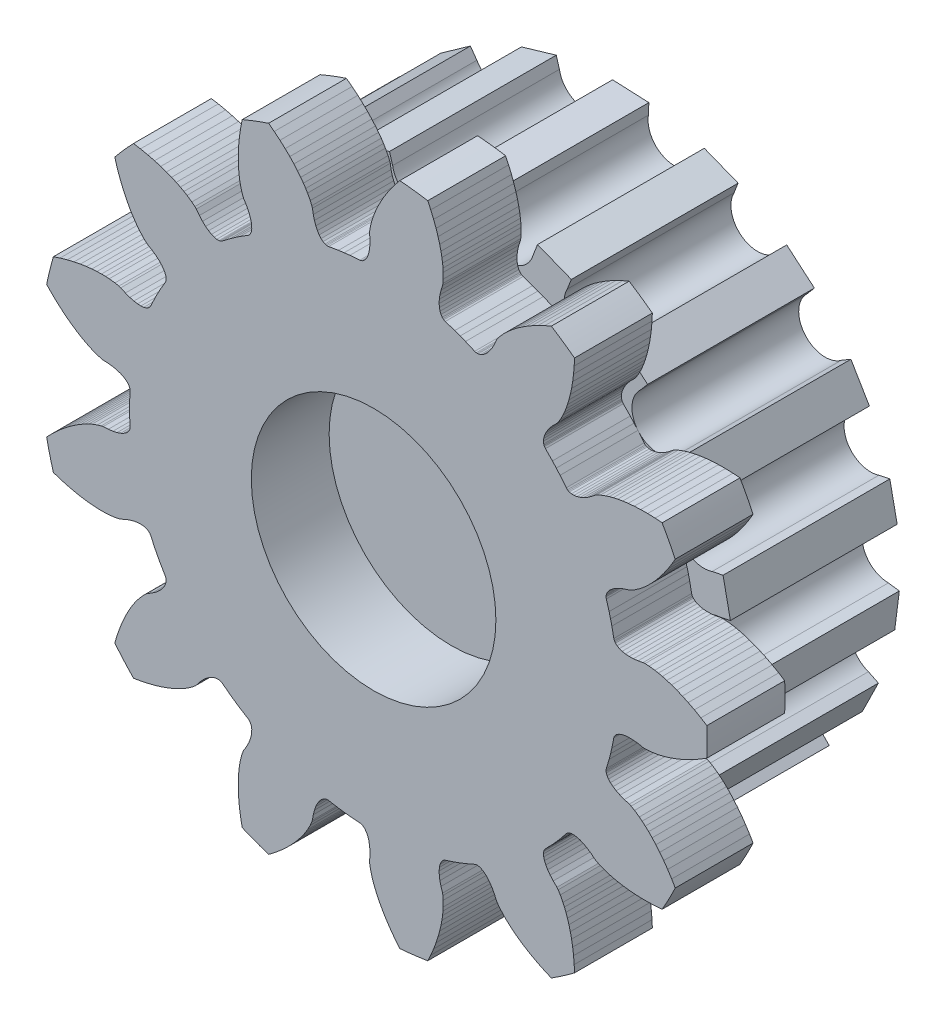
SolidWorks part; units mm, degrees
ref_plane "Front Plane" through (0, 0, 0) normal (0, 0, 1) x (1, 0, 0)
ref_plane "Top Plane" through (0, 0, 0) normal (0, 1, 0) x (1, 0, 0)
ref_plane "Right Plane" through (0, 0, 0) normal (1, 0, 0) x (0, 0, -1)
sketch "Model" plane through (0, 0, 0) normal (0, 0, 1) x (1, 0, 0)
  line L0 (54.9037, -18.3182) -> (55.119, -17.6838)
  line L1 (55.119, -17.6838) -> (55.345, -17.0995)
  line L2 (55.345, -17.0995) -> (55.5777, -16.5655)
  line L3 (55.5777, -16.5655) -> (55.8147, -16.0783)
  line L4 (55.8147, -16.0783) -> (56.0515, -15.6392)
  line L5 (56.0515, -15.6392) -> (56.2838, -15.2487)
  line L6 (56.2838, -15.2487) -> (56.5097, -14.9028)
  line L7 (56.5097, -14.9028) -> (56.7244, -14.6022)
  line L8 (56.7244, -14.6022) -> (56.9247, -14.3453)
  line L9 (56.9247, -14.3453) -> (57.2703, -13.9536)
  line L10 (57.2703, -13.9536) -> (57.526, -13.708)
  line L11 (57.526, -13.708) -> (57.6679, -13.5941)
  line L12 (57.6679, -13.5941) -> (58.066, -13.3611)
  line L13 (58.066, -13.3611) -> (58.4092, -13.1204)
  line L14 (58.4092, -13.1204) -> (58.6978, -12.8763)
  line L15 (58.6978, -12.8763) -> (58.932, -12.6328)
  line L16 (58.932, -12.6328) -> (59.1126, -12.3942)
  line L17 (59.1126, -12.3942) -> (59.2403, -12.1644)
  line L18 (59.2403, -12.1644) -> (59.3164, -11.9475)
  line L19 (59.3164, -11.9475) -> (59.3421, -11.7472)
  line L20 (59.3421, -11.7472) -> (59.3367, -11.6545)
  line L21 (59.3367, -11.6545) -> (59.3192, -11.5674)
  line L22 (59.3192, -11.5674) -> (59.2607, -11.4299)
  line L23 (59.2607, -11.4299) -> (58.8102, -10.6563)
  line L24 (58.8102, -10.6563) -> (58.5642, -10.2007)
  line L25 (58.5642, -10.2007) -> (58.329, -9.7394)
  line L26 (58.329, -9.7394) -> (57.9483, -8.9292)
  line L27 (57.9483, -8.9292) -> (57.8683, -8.8029)
  line L28 (57.8683, -8.8029) -> (57.8065, -8.7391)
  line L29 (57.8065, -8.7391) -> (57.7334, -8.6819)
  line L30 (57.7334, -8.6819) -> (57.5539, -8.5894)
  line L31 (57.5539, -8.5894) -> (57.3321, -8.5288)
  line L32 (57.3321, -8.5288) -> (57.0705, -8.5034)
  line L33 (57.0705, -8.5034) -> (56.7715, -8.5164)
  line L34 (56.7715, -8.5164) -> (56.4381, -8.5709)
  line L35 (56.4381, -8.5709) -> (56.0733, -8.6697)
  line L36 (56.0733, -8.6697) -> (55.6803, -8.8154)
  line L37 (55.6803, -8.8154) -> (55.2623, -9.0107)
  line L38 (55.2623, -9.0107) -> (55.088, -9.0628)
  line L39 (55.088, -9.0628) -> (54.7406, -9.1337)
  line L40 (54.7406, -9.1337) -> (54.2219, -9.1956)
  line L41 (54.2219, -9.1956) -> (53.8967, -9.2145)
  line L42 (53.8967, -9.2145) -> (53.5274, -9.2205)
  line L43 (53.5274, -9.2205) -> (53.1144, -9.2099)
  line L44 (53.1144, -9.2099) -> (52.6611, -9.1792)
  line L45 (52.6611, -9.1792) -> (52.1651, -9.1246)
  line L46 (52.1651, -9.1246) -> (51.6295, -9.0429)
  line L47 (51.6295, -9.0429) -> (51.0579, -8.9311)
  line L48 (51.0579, -8.9311) -> (50.4486, -8.7851)
  line L49 (50.4486, -8.7851) -> (49.8043, -8.6019)
  line L50 (49.8043, -8.6019) -> (49.2012, -8.4037)
  line L51 (48.5945, -5.9424) -> (49.0364, -5.4866)
  line L52 (49.0364, -5.4866) -> (49.5218, -5.0249)
  line L53 (49.5218, -5.0249) -> (49.9935, -4.6126)
  line L54 (49.9935, -4.6126) -> (50.4476, -4.2479)
  line L55 (50.4476, -4.2479) -> (50.8839, -3.9266)
  line L56 (50.8839, -3.9266) -> (51.2977, -3.6479)
  line L57 (51.2977, -3.6479) -> (51.6848, -3.41)
  line L58 (51.6848, -3.41) -> (52.0456, -3.2087)
  line L59 (52.0456, -3.2087) -> (52.3754, -3.0423)
  line L60 (52.3754, -3.0423) -> (52.6721, -2.9079)
  line L61 (52.6721, -2.9079) -> (53.1602, -2.7217)
  line L62 (53.1602, -2.7217) -> (53.5007, -2.623)
  line L63 (53.5007, -2.623) -> (53.6793, -2.5882)
  line L64 (53.6793, -2.5882) -> (54.1401, -2.5668)
  line L65 (54.1401, -2.5668) -> (54.5559, -2.5132)
  line L66 (54.5559, -2.5132) -> (54.9248, -2.4312)
  line L67 (54.9248, -2.4312) -> (55.2454, -2.3245)
  line L68 (55.2454, -2.3245) -> (55.5161, -2.1971)
  line L69 (55.5161, -2.1971) -> (55.736, -2.053)
  line L70 (55.736, -2.053) -> (55.9042, -1.8962)
  line L71 (55.9042, -1.8962) -> (56.0201, -1.7309)
  line L72 (56.0201, -1.7309) -> (56.0583, -1.6463)
  line L73 (56.0583, -1.6463) -> (56.0834, -1.5611)
  line L74 (56.0834, -1.5611) -> (56.0954, -1.4121)
  line L75 (56.0954, -1.4121) -> (56.056, -0.5178)
  line L76 (56.056, -0.5178) -> (56.05, 0)
  line L77 (56.05, 0) -> (56.056, 0.5178)
  line L78 (56.056, 0.5178) -> (56.0954, 1.4121)
  line L79 (56.0954, 1.4121) -> (56.0834, 1.5611)
  line L80 (56.0834, 1.5611) -> (56.0583, 1.6463)
  line L81 (56.0583, 1.6463) -> (56.0201, 1.7309)
  line L82 (56.0201, 1.7309) -> (55.9042, 1.8962)
  line L83 (55.9042, 1.8962) -> (55.736, 2.053)
  line L84 (55.736, 2.053) -> (55.5161, 2.1971)
  line L85 (55.5161, 2.1971) -> (55.2454, 2.3245)
  line L86 (55.2454, 2.3245) -> (54.9248, 2.4312)
  line L87 (54.9248, 2.4312) -> (54.5559, 2.5132)
  line L88 (54.5559, 2.5132) -> (54.1401, 2.5668)
  line L89 (54.1401, 2.5668) -> (53.6793, 2.5882)
  line L90 (53.6793, 2.5882) -> (53.5007, 2.623)
  line L91 (53.5007, 2.623) -> (53.1602, 2.7217)
  line L92 (53.1602, 2.7217) -> (52.6721, 2.9079)
  line L93 (52.6721, 2.9079) -> (52.3754, 3.0423)
  line L94 (52.3754, 3.0423) -> (52.0456, 3.2087)
  line L95 (52.0456, 3.2087) -> (51.6848, 3.41)
  line L96 (51.6848, 3.41) -> (51.2977, 3.6479)
  line L97 (51.2977, 3.6479) -> (50.8839, 3.9266)
  line L98 (50.8839, 3.9266) -> (50.4476, 4.2479)
  line L99 (50.4476, 4.2479) -> (49.9935, 4.6126)
  line L100 (49.9935, 4.6126) -> (49.5218, 5.0249)
  line L101 (49.5218, 5.0249) -> (49.0364, 5.4866)
  line L102 (49.0364, 5.4866) -> (48.5945, 5.9424)
  line L103 (49.2012, 8.4037) -> (49.8043, 8.6019)
  line L104 (49.8043, 8.6019) -> (50.4486, 8.7851)
  line L105 (50.4486, 8.7851) -> (51.0579, 8.9311)
  line L106 (51.0579, 8.9311) -> (51.6295, 9.0429)
  line L107 (51.6295, 9.0429) -> (52.1651, 9.1246)
  line L108 (52.1651, 9.1246) -> (52.6611, 9.1792)
  line L109 (52.6611, 9.1792) -> (53.1144, 9.2099)
  line L110 (53.1144, 9.2099) -> (53.5274, 9.2205)
  line L111 (53.5274, 9.2205) -> (53.8967, 9.2145)
  line L112 (53.8967, 9.2145) -> (54.2219, 9.1956)
  line L113 (54.2219, 9.1956) -> (54.7406, 9.1337)
  line L114 (54.7406, 9.1337) -> (55.088, 9.0628)
  line L115 (55.088, 9.0628) -> (55.2623, 9.0107)
  line L116 (55.2623, 9.0107) -> (55.6803, 8.8154)
  line L117 (55.6803, 8.8154) -> (56.0733, 8.6697)
  line L118 (56.0733, 8.6697) -> (56.4381, 8.5709)
  line L119 (56.4381, 8.5709) -> (56.7715, 8.5164)
  line L120 (56.7715, 8.5164) -> (57.0705, 8.5034)
  line L121 (57.0705, 8.5034) -> (57.3321, 8.5288)
  line L122 (57.3321, 8.5288) -> (57.5539, 8.5894)
  line L123 (57.5539, 8.5894) -> (57.7334, 8.6819)
  line L124 (57.7334, 8.6819) -> (57.8065, 8.7391)
  line L125 (57.8065, 8.7391) -> (57.8683, 8.8029)
  line L126 (57.8683, 8.8029) -> (57.9483, 8.9292)
  line L127 (57.9483, 8.9292) -> (58.329, 9.7394)
  line L128 (58.329, 9.7394) -> (58.5642, 10.2007)
  line L129 (58.5642, 10.2007) -> (58.8102, 10.6563)
  line L130 (58.8102, 10.6563) -> (59.2607, 11.4299)
  line L131 (59.2607, 11.4299) -> (59.3192, 11.5674)
  line L132 (59.3192, 11.5674) -> (59.3367, 11.6545)
  line L133 (59.3367, 11.6545) -> (59.3421, 11.7472)
  line L134 (59.3421, 11.7472) -> (59.3164, 11.9475)
  line L135 (59.3164, 11.9475) -> (59.2403, 12.1644)
  line L136 (59.2403, 12.1644) -> (59.1126, 12.3942)
  line L137 (59.1126, 12.3942) -> (58.932, 12.6328)
  line L138 (58.932, 12.6328) -> (58.6978, 12.8763)
  line L139 (58.6978, 12.8763) -> (58.4092, 13.1204)
  line L140 (58.4092, 13.1204) -> (58.066, 13.3611)
  line L141 (58.066, 13.3611) -> (57.6679, 13.5941)
  line L142 (57.6679, 13.5941) -> (57.526, 13.708)
  line L143 (57.526, 13.708) -> (57.2703, 13.9536)
  line L144 (57.2703, 13.9536) -> (56.9247, 14.3453)
  line L145 (56.9247, 14.3453) -> (56.7244, 14.6022)
  line L146 (56.7244, 14.6022) -> (56.5097, 14.9028)
  line L147 (56.5097, 14.9028) -> (56.2838, 15.2487)
  line L148 (56.2838, 15.2487) -> (56.0515, 15.6392)
  line L149 (56.0515, 15.6392) -> (55.8147, 16.0783)
  line L150 (55.8147, 16.0783) -> (55.5777, 16.5655)
  line L151 (55.5777, 16.5655) -> (55.345, 17.0995)
  line L152 (55.345, 17.0995) -> (55.119, 17.6838)
  line L153 (55.119, 17.6838) -> (54.9037, 18.3182)
  line L154 (54.9037, 18.3182) -> (54.7243, 18.9271)
  line L155 (56.4053, 20.8246) -> (57.0315, 20.7198)
  line L156 (57.0315, 20.7198) -> (57.6871, 20.5826)
  line L157 (57.6871, 20.5826) -> (58.2944, 20.4287)
  line L158 (58.2944, 20.4287) -> (58.8525, 20.2621)
  line L159 (58.8525, 20.2621) -> (59.3648, 20.0855)
  line L160 (59.3648, 20.0855) -> (59.8293, 19.9033)
  line L161 (59.8293, 19.9033) -> (60.2449, 19.7199)
  line L162 (60.2449, 19.7199) -> (60.6155, 19.5373)
  line L163 (60.6155, 19.5373) -> (60.9398, 19.3604)
  line L164 (60.9398, 19.3604) -> (61.219, 19.1925)
  line L165 (61.219, 19.1925) -> (61.6495, 18.8967)
  line L166 (61.6495, 18.8967) -> (61.9241, 18.6724)
  line L167 (61.9241, 18.6724) -> (62.0542, 18.5453)
  line L168 (62.0542, 18.5453) -> (62.3336, 18.1782)
  line L169 (62.3336, 18.1782) -> (62.6139, 17.8664)
  line L170 (62.6139, 17.8664) -> (62.891, 17.6094)
  line L171 (62.891, 17.6094) -> (63.1609, 17.4062)
  line L172 (63.1609, 17.4062) -> (63.4195, 17.2558)
  line L173 (63.4195, 17.2558) -> (63.663, 17.1567)
  line L174 (63.663, 17.1567) -> (63.8876, 17.1073)
  line L175 (63.8876, 17.1073) -> (64.0895, 17.1058)
  line L176 (64.0895, 17.1058) -> (64.1808, 17.1224)
  line L177 (64.1808, 17.1224) -> (64.2652, 17.1503)
  line L178 (64.2652, 17.1503) -> (64.3947, 17.225)
  line L179 (64.3947, 17.225) -> (65.1083, 17.7654)
  line L180 (65.1083, 17.7654) -> (65.531, 18.0645)
  line L181 (65.531, 18.0645) -> (65.9605, 18.3536)
  line L182 (65.9605, 18.3536) -> (66.7189, 18.8292)
  line L183 (66.7189, 18.8292) -> (66.8347, 18.9238)
  line L184 (66.8347, 18.9238) -> (66.8906, 18.9928)
  line L185 (66.8906, 18.9928) -> (66.9385, 19.0724)
  line L186 (66.9385, 19.0724) -> (67.0087, 19.2617)
  line L187 (67.0087, 19.2617) -> (67.0422, 19.4891)
  line L188 (67.0422, 19.4891) -> (67.0359, 19.752)
  line L189 (67.0359, 19.752) -> (66.9869, 20.0471)
  line L190 (66.9869, 20.0471) -> (66.8926, 20.3715)
  line L191 (66.8926, 20.3715) -> (66.7506, 20.7218)
  line L192 (66.7506, 20.7218) -> (66.5585, 21.0944)
  line L193 (66.5585, 21.0944) -> (66.3143, 21.4858)
  line L194 (66.3143, 21.4858) -> (66.2416, 21.6526)
  line L195 (66.2416, 21.6526) -> (66.1293, 21.9888)
  line L196 (66.1293, 21.9888) -> (66.0053, 22.4963)
  line L197 (66.0053, 22.4963) -> (65.9473, 22.8169)
  line L198 (65.9473, 22.8169) -> (65.8969, 23.1828)
  line L199 (65.8969, 23.1828) -> (65.8577, 23.5941)
  line L200 (65.8577, 23.5941) -> (65.8335, 24.0478)
  line L201 (65.8335, 24.0478) -> (65.8278, 24.5467)
  line L202 (65.8278, 24.5467) -> (65.8444, 25.0882)
  line L203 (65.8444, 25.0882) -> (65.8865, 25.6691)
  line L204 (65.8865, 25.6691) -> (65.958, 26.2916)
  line L205 (65.958, 26.2916) -> (66.0622, 26.9533)
  line L206 (66.0622, 26.9533) -> (66.1863, 27.5759)
  line L207 (68.5565, 28.4748) -> (69.0623, 28.0911)
  line L208 (69.0623, 28.0911) -> (69.5791, 27.6649)
  line L209 (69.5791, 27.6649) -> (70.0453, 27.2463)
  line L210 (70.0453, 27.2463) -> (70.462, 26.8395)
  line L211 (70.462, 26.8395) -> (70.8335, 26.4451)
  line L212 (70.8335, 26.4451) -> (71.1601, 26.0679)
  line L213 (71.1601, 26.0679) -> (71.4429, 25.7123)
  line L214 (71.4429, 25.7123) -> (71.6863, 25.3784)
  line L215 (71.6863, 25.3784) -> (71.8911, 25.0711)
  line L216 (71.8911, 25.0711) -> (72.0604, 24.7927)
  line L217 (72.0604, 24.7927) -> (72.3041, 24.3306)
  line L218 (72.3041, 24.3306) -> (72.443, 24.0045)
  line L219 (72.443, 24.0045) -> (72.4991, 23.8314)
  line L220 (72.4991, 23.8314) -> (72.5759, 23.3765)
  line L221 (72.5759, 23.3765) -> (72.6792, 22.9702)
  line L222 (72.6792, 22.9702) -> (72.8051, 22.6139)
  line L223 (72.8051, 22.6139) -> (72.9497, 22.3085)
  line L224 (72.9497, 22.3085) -> (73.1088, 22.0551)
  line L225 (73.1088, 22.0551) -> (73.2784, 21.8542)
  line L226 (73.2784, 21.8542) -> (73.4542, 21.7061)
  line L227 (73.4542, 21.7061) -> (73.6323, 21.611)
  line L228 (73.6323, 21.611) -> (73.7209, 21.5833)
  line L229 (73.7209, 21.5833) -> (73.8085, 21.5687)
  line L230 (73.8085, 21.5687) -> (73.9579, 21.5746)
  line L231 (73.9579, 21.5746) -> (74.841, 21.7216)
  line L232 (74.841, 21.7216) -> (75.3542, 21.79)
  line L233 (75.3542, 21.79) -> (75.8689, 21.8464)
  line L234 (75.8689, 21.8464) -> (76.7615, 21.9151)
  line L235 (76.7615, 21.9151) -> (76.9079, 21.945)
  line L236 (76.9079, 21.945) -> (76.9895, 21.9801)
  line L237 (76.9895, 21.9801) -> (77.0689, 22.0283)
  line L238 (77.0689, 22.0283) -> (77.2191, 22.1633)
  line L239 (77.2191, 22.1633) -> (77.3544, 22.3491)
  line L240 (77.3544, 22.3491) -> (77.4709, 22.5848)
  line L241 (77.4709, 22.5848) -> (77.5648, 22.8689)
  line L242 (77.5648, 22.8689) -> (77.6321, 23.2)
  line L243 (77.6321, 23.2) -> (77.669, 23.5761)
  line L244 (77.669, 23.5761) -> (77.6721, 23.9953)
  line L245 (77.6721, 23.9953) -> (77.6378, 24.4554)
  line L246 (77.6378, 24.4554) -> (77.6509, 24.6368)
  line L247 (77.6509, 24.6368) -> (77.7077, 24.9868)
  line L248 (77.7077, 24.9868) -> (77.8338, 25.4937)
  line L249 (77.8338, 25.4937) -> (77.9314, 25.8045)
  line L250 (77.9314, 25.8045) -> (78.0568, 26.1519)
  line L251 (78.0568, 26.1519) -> (78.2132, 26.5343)
  line L252 (78.2132, 26.5343) -> (78.4026, 26.9473)
  line L253 (78.4026, 26.9473) -> (78.6295, 27.3917)
  line L254 (78.6295, 27.3917) -> (78.8958, 27.8635)
  line L255 (78.8958, 27.8635) -> (79.2031, 28.3583)
  line L256 (79.2031, 28.3583) -> (79.5556, 28.8762)
  line L257 (79.5556, 28.8762) -> (79.9554, 29.4137)
  line L258 (79.9554, 29.4137) -> (80.3546, 29.9073)
  line L259 (82.8711, 29.6018) -> (83.1406, 29.027)
  line L260 (83.1406, 29.027) -> (83.4001, 28.4094)
  line L261 (83.4001, 28.4094) -> (83.6184, 27.8222)
  line L262 (83.6184, 27.8222) -> (83.7984, 27.2683)
  line L263 (83.7984, 27.2683) -> (83.9441, 26.7464)
  line L264 (83.9441, 26.7464) -> (84.058, 26.2606)
  line L265 (84.058, 26.2606) -> (84.1431, 25.8143)
  line L266 (84.1431, 25.8143) -> (84.2034, 25.4056)
  line L267 (84.2034, 25.4056) -> (84.242, 25.0383)
  line L268 (84.242, 25.0383) -> (84.2624, 24.7131)
  line L269 (84.2624, 24.7131) -> (84.2635, 24.1907)
  line L270 (84.2635, 24.1907) -> (84.235, 23.8373)
  line L271 (84.235, 23.8373) -> (84.2043, 23.6581)
  line L272 (84.2043, 23.6581) -> (84.0608, 23.2196)
  line L273 (84.0608, 23.2196) -> (83.9635, 22.8118)
  line L274 (83.9635, 22.8118) -> (83.9094, 22.4377)
  line L275 (83.9094, 22.4377) -> (83.8955, 22.1002)
  line L276 (83.8955, 22.1002) -> (83.9186, 21.8019)
  line L277 (83.9186, 21.8019) -> (83.9753, 21.5452)
  line L278 (83.9753, 21.5452) -> (84.0623, 21.3323)
  line L279 (84.0623, 21.3323) -> (84.1758, 21.1653)
  line L280 (84.1758, 21.1653) -> (84.2413, 21.0996)
  line L281 (84.2413, 21.0996) -> (84.3121, 21.046)
  line L282 (84.3121, 21.046) -> (84.4472, 20.9818)
  line L283 (84.4472, 20.9818) -> (85.2973, 20.7016)
  line L284 (85.2973, 20.7016) -> (85.7836, 20.5236)
  line L285 (85.7836, 20.5236) -> (86.2655, 20.3344)
  line L286 (86.2655, 20.3344) -> (87.0878, 19.9804)
  line L287 (87.0878, 19.9804) -> (87.2314, 19.9389)
  line L288 (87.2314, 19.9389) -> (87.3199, 19.932)
  line L289 (87.3199, 19.932) -> (87.4126, 19.9378)
  line L290 (87.4126, 19.9378) -> (87.6083, 19.9875)
  line L291 (87.6083, 19.9875) -> (87.8145, 20.0892)
  line L292 (87.8145, 20.0892) -> (88.0272, 20.2437)
  line L293 (88.0272, 20.2437) -> (88.2423, 20.4517)
  line L294 (88.2423, 20.4517) -> (88.4558, 20.7135)
  line L295 (88.4558, 20.7135) -> (88.6633, 21.0294)
  line L296 (88.6633, 21.0294) -> (88.8609, 21.3992)
  line L297 (88.8609, 21.3992) -> (89.0442, 21.8225)
  line L298 (89.0442, 21.8225) -> (89.1401, 21.9771)
  line L299 (89.1401, 21.9771) -> (89.3531, 22.2605)
  line L300 (89.3531, 22.2605) -> (89.7003, 22.6508)
  line L301 (89.7003, 22.6508) -> (89.9312, 22.8806)
  line L302 (89.9312, 22.8806) -> (90.2037, 23.13)
  line L303 (90.2037, 23.13) -> (90.5199, 23.3959)
  line L304 (90.5199, 23.3959) -> (90.8796, 23.6735)
  line L305 (90.8796, 23.6735) -> (91.2869, 23.9616)
  line L306 (91.2869, 23.9616) -> (91.742, 24.2556)
  line L307 (91.742, 24.2556) -> (92.2441, 24.5509)
  line L308 (92.2441, 24.5509) -> (92.7969, 24.8457)
  line L309 (92.7969, 24.8457) -> (93.4007, 25.1359)
  line L310 (93.4007, 25.1359) -> (93.9836, 25.3874)
  line L311 (96.0698, 23.9474) -> (96.0413, 23.3132)
  line L312 (96.0413, 23.3132) -> (95.9841, 22.6457)
  line L313 (95.9841, 22.6457) -> (95.9045, 22.0243)
  line L314 (95.9045, 22.0243) -> (95.8064, 21.4502)
  line L315 (95.8064, 21.4502) -> (95.6929, 20.9204)
  line L316 (95.6929, 20.9204) -> (95.568, 20.4373)
  line L317 (95.568, 20.4373) -> (95.4359, 20.0026)
  line L318 (95.4359, 20.0026) -> (95.2994, 19.6127)
  line L319 (95.2994, 19.6127) -> (95.1629, 19.2695)
  line L320 (95.1629, 19.2695) -> (95.0299, 18.9721)
  line L321 (95.0299, 18.9721) -> (94.7881, 18.509)
  line L322 (94.7881, 18.509) -> (94.5986, 18.2094)
  line L323 (94.5986, 18.2094) -> (94.488, 18.0649)
  line L324 (94.488, 18.0649) -> (94.1573, 17.7433)
  line L325 (94.1573, 17.7433) -> (93.8816, 17.4275)
  line L326 (93.8816, 17.4275) -> (93.6598, 17.1214)
  line L327 (93.6598, 17.1214) -> (93.4907, 16.829)
  line L328 (93.4907, 16.829) -> (93.3725, 16.5541)
  line L329 (93.3725, 16.5541) -> (93.3035, 16.3004)
  line L330 (93.3035, 16.3004) -> (93.2815, 16.0716)
  line L331 (93.2815, 16.0716) -> (93.3044, 15.871)
  line L332 (93.3044, 15.871) -> (93.3319, 15.7823)
  line L333 (93.3319, 15.7823) -> (93.3697, 15.7019)
  line L334 (93.3697, 15.7019) -> (93.4594, 15.5824)
  line L335 (93.4594, 15.5824) -> (94.082, 14.9391)
  line L336 (94.082, 14.9391) -> (94.4298, 14.5555)
  line L337 (94.4298, 14.5555) -> (94.7686, 14.164)
  line L338 (94.7686, 14.164) -> (95.3322, 13.4685)
  line L339 (95.3322, 13.4685) -> (95.44, 13.3649)
  line L340 (95.44, 13.3649) -> (95.5153, 13.3178)
  line L341 (95.5153, 13.3178) -> (95.6, 13.2798)
  line L342 (95.6, 13.2798) -> (95.7964, 13.2329)
  line L343 (95.7964, 13.2329) -> (96.0262, 13.2271)
  line L344 (96.0262, 13.2271) -> (96.2864, 13.265)
  line L345 (96.2864, 13.265) -> (96.5735, 13.3492)
  line L346 (96.5735, 13.3492) -> (96.8842, 13.4819)
  line L347 (96.8842, 13.4819) -> (97.2147, 13.6651)
  line L348 (97.2147, 13.6651) -> (97.5615, 13.9007)
  line L349 (97.5615, 13.9007) -> (97.9206, 14.1903)
  line L350 (97.9206, 14.1903) -> (98.0774, 14.2826)
  line L351 (98.0774, 14.2826) -> (98.3977, 14.4346)
  line L352 (98.3977, 14.4346) -> (98.8865, 14.6189)
  line L353 (98.8865, 14.6189) -> (99.1977, 14.7151)
  line L354 (99.1977, 14.7151) -> (99.5549, 14.8092)
  line L355 (99.5549, 14.8092) -> (99.9585, 14.8978)
  line L356 (99.9585, 14.8978) -> (100.4059, 14.9764)
  line L357 (100.4059, 14.9764) -> (100.9005, 15.0422)
  line L358 (100.9005, 15.0422) -> (101.4401, 15.091)
  line L359 (101.4401, 15.091) -> (102.0219, 15.1192)
  line L360 (102.0219, 15.1192) -> (102.6484, 15.1233)
  line L361 (102.6484, 15.1233) -> (103.3178, 15.0997)
  line L362 (103.3178, 15.0997) -> (103.9508, 15.0515)
  line L363 (105.1289, 12.8069) -> (104.8089, 12.2586)
  line L364 (104.8089, 12.2586) -> (104.4481, 11.6942)
  line L365 (104.4481, 11.6942) -> (104.0888, 11.1809)
  line L366 (104.0888, 11.1809) -> (103.7352, 10.7182)
  line L367 (103.7352, 10.7182) -> (103.3885, 10.3018)
  line L368 (103.3885, 10.3018) -> (103.0534, 9.9321)
  line L369 (103.0534, 9.9321) -> (102.7344, 9.6086)
  line L370 (102.7344, 9.6086) -> (102.4323, 9.3267)
  line L371 (102.4323, 9.3267) -> (102.1519, 9.0863)
  line L372 (102.1519, 9.0863) -> (101.896, 8.8848)
  line L373 (101.896, 8.8848) -> (101.4667, 8.5871)
  line L374 (101.4667, 8.5871) -> (101.1596, 8.4099)
  line L375 (101.1596, 8.4099) -> (100.9946, 8.3333)
  line L376 (100.9946, 8.3333) -> (100.5523, 8.2023)
  line L377 (100.5523, 8.2023) -> (100.1614, 8.0508)
  line L378 (100.1614, 8.0508) -> (99.8228, 7.8828)
  line L379 (99.8228, 7.8828) -> (99.5371, 7.7025)
  line L380 (99.5371, 7.7025) -> (99.3047, 7.514)
  line L381 (99.3047, 7.514) -> (99.1257, 7.3215)
  line L382 (99.1257, 7.3215) -> (98.9999, 7.129)
  line L383 (98.9999, 7.129) -> (98.927, 6.9407)
  line L384 (98.927, 6.9407) -> (98.9101, 6.8494)
  line L385 (98.9101, 6.8494) -> (98.9062, 6.7607)
  line L386 (98.9062, 6.7607) -> (98.9301, 6.6131)
  line L387 (98.9301, 6.6131) -> (99.1824, 5.7542)
  line L388 (99.1824, 5.7542) -> (99.3122, 5.253)
  line L389 (99.3122, 5.253) -> (99.4302, 4.7488)
  line L390 (99.4302, 4.7488) -> (99.606, 3.8711)
  line L391 (99.606, 3.8711) -> (99.6534, 3.7293)
  line L392 (99.6534, 3.7293) -> (99.6981, 3.6525)
  line L393 (99.6981, 3.6525) -> (99.7554, 3.5795)
  line L394 (99.7554, 3.5795) -> (99.9075, 3.4467)
  line L395 (99.9075, 3.4467) -> (100.1084, 3.3348)
  line L396 (100.1084, 3.3348) -> (100.3563, 3.2475)
  line L397 (100.3563, 3.2475) -> (100.6497, 3.1886)
  line L398 (100.6497, 3.1886) -> (100.9864, 3.1617)
  line L399 (100.9864, 3.1617) -> (101.3643, 3.1703)
  line L400 (101.3643, 3.1703) -> (101.7808, 3.2178)
  line L401 (101.7808, 3.2178) -> (102.2334, 3.3073)
  line L402 (102.2334, 3.3073) -> (102.4151, 3.3162)
  line L403 (102.4151, 3.3162) -> (102.7693, 3.302)
  line L404 (102.7693, 3.302) -> (103.2878, 3.238)
  line L405 (103.2878, 3.238) -> (103.6081, 3.1784)
  line L406 (103.6081, 3.1784) -> (103.9681, 3.0959)
  line L407 (103.9681, 3.0959) -> (104.3666, 2.9867)
  line L408 (104.3666, 2.9867) -> (104.7993, 2.8484)
  line L409 (104.7993, 2.8484) -> (105.2679, 2.6768)
  line L410 (105.2679, 2.6768) -> (105.7684, 2.4693)
  line L411 (105.7684, 2.4693) -> (106.2966, 2.2239)
  line L412 (106.2966, 2.2239) -> (106.8532, 1.9364)
  line L413 (106.8532, 1.9364) -> (107.435, 1.6043)
  line L414 (107.435, 1.6043) -> (107.9731, 1.2675)
  line L415 (107.9731, -1.2675) -> (107.435, -1.6043)
  line L416 (107.435, -1.6043) -> (106.8532, -1.9364)
  line L417 (106.8532, -1.9364) -> (106.2966, -2.2239)
  line L418 (106.2966, -2.2239) -> (105.7684, -2.4693)
  line L419 (105.7684, -2.4693) -> (105.2679, -2.6768)
  line L420 (105.2679, -2.6768) -> (104.7993, -2.8484)
  line L421 (104.7993, -2.8484) -> (104.3666, -2.9867)
  line L422 (104.3666, -2.9867) -> (103.9681, -3.0959)
  line L423 (103.9681, -3.0959) -> (103.6081, -3.1784)
  line L424 (103.6081, -3.1784) -> (103.2878, -3.238)
  line L425 (103.2878, -3.238) -> (102.7693, -3.302)
  line L426 (102.7693, -3.302) -> (102.4151, -3.3162)
  line L427 (102.4151, -3.3162) -> (102.2334, -3.3073)
  line L428 (102.2334, -3.3073) -> (101.7808, -3.2178)
  line L429 (101.7808, -3.2178) -> (101.3643, -3.1703)
  line L430 (101.3643, -3.1703) -> (100.9864, -3.1617)
  line L431 (100.9864, -3.1617) -> (100.6497, -3.1886)
  line L432 (100.6497, -3.1886) -> (100.3563, -3.2475)
  line L433 (100.3563, -3.2475) -> (100.1084, -3.3348)
  line L434 (100.1084, -3.3348) -> (99.9075, -3.4467)
  line L435 (99.9075, -3.4467) -> (99.7554, -3.5795)
  line L436 (99.7554, -3.5795) -> (99.6981, -3.6525)
  line L437 (99.6981, -3.6525) -> (99.6534, -3.7293)
  line L438 (99.6534, -3.7293) -> (99.606, -3.8711)
  line L439 (99.606, -3.8711) -> (99.4302, -4.7488)
  line L440 (99.4302, -4.7488) -> (99.3122, -5.253)
  line L441 (99.3122, -5.253) -> (99.1824, -5.7542)
  line L442 (99.1824, -5.7542) -> (98.9301, -6.6131)
  line L443 (98.9301, -6.6131) -> (98.9062, -6.7607)
  line L444 (98.9062, -6.7607) -> (98.9101, -6.8494)
  line L445 (98.9101, -6.8494) -> (98.927, -6.9407)
  line L446 (98.927, -6.9407) -> (98.9999, -7.129)
  line L447 (98.9999, -7.129) -> (99.1257, -7.3215)
  line L448 (99.1257, -7.3215) -> (99.3047, -7.514)
  line L449 (99.3047, -7.514) -> (99.5371, -7.7025)
  line L450 (99.5371, -7.7025) -> (99.8228, -7.8828)
  line L451 (99.8228, -7.8828) -> (100.1614, -8.0508)
  line L452 (100.1614, -8.0508) -> (100.5523, -8.2023)
  line L453 (100.5523, -8.2023) -> (100.9946, -8.3333)
  line L454 (100.9946, -8.3333) -> (101.1596, -8.4099)
  line L455 (101.1596, -8.4099) -> (101.4667, -8.5871)
  line L456 (101.4667, -8.5871) -> (101.896, -8.8848)
  line L457 (101.896, -8.8848) -> (102.1519, -9.0863)
  line L458 (102.1519, -9.0863) -> (102.4323, -9.3267)
  line L459 (102.4323, -9.3267) -> (102.7344, -9.6086)
  line L460 (102.7344, -9.6086) -> (103.0534, -9.9321)
  line L461 (103.0534, -9.9321) -> (103.3885, -10.3018)
  line L462 (103.3885, -10.3018) -> (103.7352, -10.7182)
  line L463 (103.7352, -10.7182) -> (104.0888, -11.1809)
  line L464 (104.0888, -11.1809) -> (104.4481, -11.6942)
  line L465 (104.4481, -11.6942) -> (104.8089, -12.2586)
  line L466 (104.8089, -12.2586) -> (105.1289, -12.8069)
  line L467 (103.9508, -15.0515) -> (103.3178, -15.0997)
  line L468 (103.3178, -15.0997) -> (102.6484, -15.1233)
  line L469 (102.6484, -15.1233) -> (102.0219, -15.1192)
  line L470 (102.0219, -15.1192) -> (101.4401, -15.091)
  line L471 (101.4401, -15.091) -> (100.9005, -15.0422)
  line L472 (100.9005, -15.0422) -> (100.4059, -14.9764)
  line L473 (100.4059, -14.9764) -> (99.9585, -14.8978)
  line L474 (99.9585, -14.8978) -> (99.5549, -14.8092)
  line L475 (99.5549, -14.8092) -> (99.1977, -14.7151)
  line L476 (99.1977, -14.7151) -> (98.8865, -14.6189)
  line L477 (98.8865, -14.6189) -> (98.3977, -14.4346)
  line L478 (98.3977, -14.4346) -> (98.0774, -14.2826)
  line L479 (98.0774, -14.2826) -> (97.9206, -14.1903)
  line L480 (97.9206, -14.1903) -> (97.5615, -13.9007)
  line L481 (97.5615, -13.9007) -> (97.2147, -13.6651)
  line L482 (97.2147, -13.6651) -> (96.8842, -13.4819)
  line L483 (96.8842, -13.4819) -> (96.5735, -13.3492)
  line L484 (96.5735, -13.3492) -> (96.2864, -13.265)
  line L485 (96.2864, -13.265) -> (96.0262, -13.2271)
  line L486 (96.0262, -13.2271) -> (95.7964, -13.2329)
  line L487 (95.7964, -13.2329) -> (95.6, -13.2798)
  line L488 (95.6, -13.2798) -> (95.5153, -13.3178)
  line L489 (95.5153, -13.3178) -> (95.44, -13.3649)
  line L490 (95.44, -13.3649) -> (95.3322, -13.4685)
  line L491 (95.3322, -13.4685) -> (94.7686, -14.164)
  line L492 (94.7686, -14.164) -> (94.4298, -14.5555)
  line L493 (94.4298, -14.5555) -> (94.082, -14.9391)
  line L494 (94.082, -14.9391) -> (93.4594, -15.5824)
  line L495 (93.4594, -15.5824) -> (93.3697, -15.7019)
  line L496 (93.3697, -15.7019) -> (93.3319, -15.7823)
  line L497 (93.3319, -15.7823) -> (93.3044, -15.871)
  line L498 (93.3044, -15.871) -> (93.2815, -16.0716)
  line L499 (93.2815, -16.0716) -> (93.3035, -16.3004)
  line L500 (93.3035, -16.3004) -> (93.3725, -16.5541)
  line L501 (93.3725, -16.5541) -> (93.4907, -16.829)
  line L502 (93.4907, -16.829) -> (93.6598, -17.1214)
  line L503 (93.6598, -17.1214) -> (93.8816, -17.4275)
  line L504 (93.8816, -17.4275) -> (94.1573, -17.7433)
  line L505 (94.1573, -17.7433) -> (94.488, -18.0649)
  line L506 (94.488, -18.0649) -> (94.5986, -18.2094)
  line L507 (94.5986, -18.2094) -> (94.7881, -18.509)
  line L508 (94.7881, -18.509) -> (95.0299, -18.9721)
  line L509 (95.0299, -18.9721) -> (95.1629, -19.2695)
  line L510 (95.1629, -19.2695) -> (95.2994, -19.6127)
  line L511 (95.2994, -19.6127) -> (95.4359, -20.0026)
  line L512 (95.4359, -20.0026) -> (95.568, -20.4373)
  line L513 (95.568, -20.4373) -> (95.6929, -20.9204)
  line L514 (95.6929, -20.9204) -> (95.8064, -21.4502)
  line L515 (95.8064, -21.4502) -> (95.9045, -22.0243)
  line L516 (95.9045, -22.0243) -> (95.9841, -22.6457)
  line L517 (95.9841, -22.6457) -> (96.0413, -23.3132)
  line L518 (96.0413, -23.3132) -> (96.0698, -23.9474)
  line L519 (93.9836, -25.3874) -> (93.4007, -25.1359)
  line L520 (93.4007, -25.1359) -> (92.7969, -24.8457)
  line L521 (92.7969, -24.8457) -> (92.2441, -24.5509)
  line L522 (92.2441, -24.5509) -> (91.742, -24.2556)
  line L523 (91.742, -24.2556) -> (91.2869, -23.9616)
  line L524 (91.2869, -23.9616) -> (90.8796, -23.6735)
  line L525 (90.8796, -23.6735) -> (90.5199, -23.3959)
  line L526 (90.5199, -23.3959) -> (90.2037, -23.13)
  line L527 (90.2037, -23.13) -> (89.9312, -22.8806)
  line L528 (89.9312, -22.8806) -> (89.7003, -22.6508)
  line L529 (89.7003, -22.6508) -> (89.3531, -22.2605)
  line L530 (89.3531, -22.2605) -> (89.1401, -21.9771)
  line L531 (89.1401, -21.9771) -> (89.0442, -21.8225)
  line L532 (89.0442, -21.8225) -> (88.8609, -21.3992)
  line L533 (88.8609, -21.3992) -> (88.6633, -21.0294)
  line L534 (88.6633, -21.0294) -> (88.4558, -20.7135)
  line L535 (88.4558, -20.7135) -> (88.2423, -20.4517)
  line L536 (88.2423, -20.4517) -> (88.0272, -20.2437)
  line L537 (88.0272, -20.2437) -> (87.8145, -20.0892)
  line L538 (87.8145, -20.0892) -> (87.6083, -19.9875)
  line L539 (87.6083, -19.9875) -> (87.4126, -19.9378)
  line L540 (87.4126, -19.9378) -> (87.3199, -19.932)
  line L541 (87.3199, -19.932) -> (87.2314, -19.9389)
  line L542 (87.2314, -19.9389) -> (87.0878, -19.9804)
  line L543 (87.0878, -19.9804) -> (86.2655, -20.3344)
  line L544 (86.2655, -20.3344) -> (85.7836, -20.5236)
  line L545 (85.7836, -20.5236) -> (85.2973, -20.7016)
  line L546 (85.2973, -20.7016) -> (84.4472, -20.9818)
  line L547 (84.4472, -20.9818) -> (84.3121, -21.046)
  line L548 (84.3121, -21.046) -> (84.2413, -21.0996)
  line L549 (84.2413, -21.0996) -> (84.1758, -21.1653)
  line L550 (84.1758, -21.1653) -> (84.0623, -21.3323)
  line L551 (84.0623, -21.3323) -> (83.9753, -21.5452)
  line L552 (83.9753, -21.5452) -> (83.9186, -21.8019)
  line L553 (83.9186, -21.8019) -> (83.8955, -22.1002)
  line L554 (83.8955, -22.1002) -> (83.9094, -22.4377)
  line L555 (83.9094, -22.4377) -> (83.9635, -22.8118)
  line L556 (83.9635, -22.8118) -> (84.0608, -23.2196)
  line L557 (84.0608, -23.2196) -> (84.2043, -23.6581)
  line L558 (84.2043, -23.6581) -> (84.235, -23.8373)
  line L559 (84.235, -23.8373) -> (84.2635, -24.1907)
  line L560 (84.2635, -24.1907) -> (84.2624, -24.7131)
  line L561 (84.2624, -24.7131) -> (84.242, -25.0383)
  line L562 (84.242, -25.0383) -> (84.2034, -25.4056)
  line L563 (84.2034, -25.4056) -> (84.1431, -25.8143)
  line L564 (84.1431, -25.8143) -> (84.058, -26.2606)
  line L565 (84.058, -26.2606) -> (83.9441, -26.7464)
  line L566 (83.9441, -26.7464) -> (83.7984, -27.2683)
  line L567 (83.7984, -27.2683) -> (83.6184, -27.8222)
  line L568 (83.6184, -27.8222) -> (83.4001, -28.4094)
  line L569 (83.4001, -28.4094) -> (83.1406, -29.027)
  line L570 (83.1406, -29.027) -> (82.8711, -29.6018)
  line L571 (80.3546, -29.9073) -> (79.9554, -29.4137)
  line L572 (79.9554, -29.4137) -> (79.5556, -28.8762)
  line L573 (79.5556, -28.8762) -> (79.2031, -28.3583)
  line L574 (79.2031, -28.3583) -> (78.8958, -27.8635)
  line L575 (78.8958, -27.8635) -> (78.6295, -27.3917)
  line L576 (78.6295, -27.3917) -> (78.4026, -26.9473)
  line L577 (78.4026, -26.9473) -> (78.2132, -26.5343)
  line L578 (78.2132, -26.5343) -> (78.0568, -26.1519)
  line L579 (78.0568, -26.1519) -> (77.9314, -25.8045)
  line L580 (77.9314, -25.8045) -> (77.8338, -25.4937)
  line L581 (77.8338, -25.4937) -> (77.7077, -24.9868)
  line L582 (77.7077, -24.9868) -> (77.6509, -24.6368)
  line L583 (77.6509, -24.6368) -> (77.6378, -24.4554)
  line L584 (77.6378, -24.4554) -> (77.6721, -23.9953)
  line L585 (77.6721, -23.9953) -> (77.669, -23.5761)
  line L586 (77.669, -23.5761) -> (77.6321, -23.2)
  line L587 (77.6321, -23.2) -> (77.5648, -22.8689)
  line L588 (77.5648, -22.8689) -> (77.4709, -22.5848)
  line L589 (77.4709, -22.5848) -> (77.3544, -22.3491)
  line L590 (77.3544, -22.3491) -> (77.2191, -22.1633)
  line L591 (77.2191, -22.1633) -> (77.0689, -22.0283)
  line L592 (77.0689, -22.0283) -> (76.9895, -21.9801)
  line L593 (76.9895, -21.9801) -> (76.9079, -21.945)
  line L594 (76.9079, -21.945) -> (76.7615, -21.9151)
  line L595 (76.7615, -21.9151) -> (75.8689, -21.8464)
  line L596 (75.8689, -21.8464) -> (75.3542, -21.79)
  line L597 (75.3542, -21.79) -> (74.841, -21.7216)
  line L598 (74.841, -21.7216) -> (73.9579, -21.5746)
  line L599 (73.9579, -21.5746) -> (73.8085, -21.5687)
  line L600 (73.8085, -21.5687) -> (73.7209, -21.5833)
  line L601 (73.7209, -21.5833) -> (73.6323, -21.611)
  line L602 (73.6323, -21.611) -> (73.4542, -21.7061)
  line L603 (73.4542, -21.7061) -> (73.2784, -21.8542)
  line L604 (73.2784, -21.8542) -> (73.1088, -22.0551)
  line L605 (73.1088, -22.0551) -> (72.9497, -22.3085)
  line L606 (72.9497, -22.3085) -> (72.8051, -22.6139)
  line L607 (72.8051, -22.6139) -> (72.6792, -22.9702)
  line L608 (72.6792, -22.9702) -> (72.5759, -23.3765)
  line L609 (72.5759, -23.3765) -> (72.4991, -23.8314)
  line L610 (72.4991, -23.8314) -> (72.443, -24.0045)
  line L611 (72.443, -24.0045) -> (72.3041, -24.3306)
  line L612 (72.3041, -24.3306) -> (72.0604, -24.7927)
  line L613 (72.0604, -24.7927) -> (71.8911, -25.0711)
  line L614 (71.8911, -25.0711) -> (71.6863, -25.3784)
  line L615 (71.6863, -25.3784) -> (71.4429, -25.7123)
  line L616 (71.4429, -25.7123) -> (71.1601, -26.0679)
  line L617 (71.1601, -26.0679) -> (70.8335, -26.4451)
  line L618 (70.8335, -26.4451) -> (70.462, -26.8395)
  line L619 (70.462, -26.8395) -> (70.0453, -27.2463)
  line L620 (70.0453, -27.2463) -> (69.5791, -27.6649)
  line L621 (69.5791, -27.6649) -> (69.0623, -28.0911)
  line L622 (69.0623, -28.0911) -> (68.5565, -28.4748)
  line L623 (66.1863, -27.5759) -> (66.0622, -26.9533)
  line L624 (66.0622, -26.9533) -> (65.958, -26.2916)
  line L625 (65.958, -26.2916) -> (65.8865, -25.6691)
  line L626 (65.8865, -25.6691) -> (65.8444, -25.0882)
  line L627 (65.8444, -25.0882) -> (65.8278, -24.5467)
  line L628 (65.8278, -24.5467) -> (65.8335, -24.0478)
  line L629 (65.8335, -24.0478) -> (65.8577, -23.5941)
  line L630 (65.8577, -23.5941) -> (65.8969, -23.1828)
  line L631 (65.8969, -23.1828) -> (65.9473, -22.8169)
  line L632 (65.9473, -22.8169) -> (66.0053, -22.4963)
  line L633 (66.0053, -22.4963) -> (66.1293, -21.9888)
  line L634 (66.1293, -21.9888) -> (66.2416, -21.6526)
  line L635 (66.2416, -21.6526) -> (66.3143, -21.4858)
  line L636 (66.3143, -21.4858) -> (66.5585, -21.0944)
  line L637 (66.5585, -21.0944) -> (66.7506, -20.7218)
  line L638 (66.7506, -20.7218) -> (66.8926, -20.3715)
  line L639 (66.8926, -20.3715) -> (66.9869, -20.0471)
  line L640 (66.9869, -20.0471) -> (67.0359, -19.752)
  line L641 (67.0359, -19.752) -> (67.0422, -19.4891)
  line L642 (67.0422, -19.4891) -> (67.0087, -19.2617)
  line L643 (67.0087, -19.2617) -> (66.9385, -19.0724)
  line L644 (66.9385, -19.0724) -> (66.8906, -18.9928)
  line L645 (66.8906, -18.9928) -> (66.8347, -18.9238)
  line L646 (66.8347, -18.9238) -> (66.7189, -18.8292)
  line L647 (66.7189, -18.8292) -> (65.9605, -18.3536)
  line L648 (65.9605, -18.3536) -> (65.531, -18.0645)
  line L649 (65.531, -18.0645) -> (65.1083, -17.7654)
  line L650 (65.1083, -17.7654) -> (64.3947, -17.225)
  line L651 (64.3947, -17.225) -> (64.2652, -17.1503)
  line L652 (64.2652, -17.1503) -> (64.1808, -17.1224)
  line L653 (64.1808, -17.1224) -> (64.0895, -17.1058)
  line L654 (64.0895, -17.1058) -> (63.8876, -17.1073)
  line L655 (63.8876, -17.1073) -> (63.663, -17.1567)
  line L656 (63.663, -17.1567) -> (63.4195, -17.2558)
  line L657 (63.4195, -17.2558) -> (63.1609, -17.4062)
  line L658 (63.1609, -17.4062) -> (62.891, -17.6094)
  line L659 (62.891, -17.6094) -> (62.6139, -17.8664)
  line L660 (62.6139, -17.8664) -> (62.3336, -18.1782)
  line L661 (62.3336, -18.1782) -> (62.0542, -18.5453)
  line L662 (62.0542, -18.5453) -> (61.9241, -18.6724)
  line L663 (61.9241, -18.6724) -> (61.6495, -18.8967)
  line L664 (61.6495, -18.8967) -> (61.219, -19.1925)
  line L665 (61.219, -19.1925) -> (60.9398, -19.3604)
  line L666 (60.9398, -19.3604) -> (60.6155, -19.5373)
  line L667 (60.6155, -19.5373) -> (60.2449, -19.7199)
  line L668 (60.2449, -19.7199) -> (59.8293, -19.9033)
  line L669 (59.8293, -19.9033) -> (59.3648, -20.0855)
  line L670 (59.3648, -20.0855) -> (58.8525, -20.2621)
  line L671 (58.8525, -20.2621) -> (58.2944, -20.4287)
  line L672 (58.2944, -20.4287) -> (57.6871, -20.5826)
  line L673 (57.6871, -20.5826) -> (57.0315, -20.7198)
  line L674 (57.0315, -20.7198) -> (56.4053, -20.8246)
  line L675 (54.7243, -18.9271) -> (54.9037, -18.3182)
  circle A1 centre (78, 0) radius 0.75
  arc A2 (48.5945, -5.9424) -> (49.2012, -8.4037) centre (78.0001, 0) ccw
  arc A3 (49.2012, 8.4037) -> (48.5945, 5.9424) centre (78.0001, 0) ccw
  arc A4 (56.4053, 20.8246) -> (54.7243, 18.9271) centre (78.0001, -0.0001) ccw
  arc A5 (68.5565, 28.4748) -> (66.1863, 27.5759) centre (78, -0.0001) ccw
  arc A6 (82.8711, 29.6018) -> (80.3546, 29.9073) centre (78, -0.0001) ccw
  arc A7 (96.0698, 23.9474) -> (93.9836, 25.3874) centre (77.9999, -0.0001) ccw
  arc A8 (105.1289, 12.8069) -> (103.9508, 15.0515) centre (77.9999, -0.0001) ccw
  arc A9 (107.9731, -1.2675) -> (107.9731, 1.2675) centre (77.9999, 0) ccw
  arc A10 (103.9508, -15.0515) -> (105.1289, -12.8069) centre (77.9999, 0.0001) ccw
  arc A11 (93.9836, -25.3874) -> (96.0698, -23.9474) centre (77.9999, 0.0001) ccw
  arc A12 (80.3546, -29.9073) -> (82.8711, -29.6018) centre (78, 0.0001) ccw
  arc A13 (66.1863, -27.5759) -> (68.5565, -28.4748) centre (78, 0.0001) ccw
  arc A14 (54.7243, -18.9271) -> (56.4053, -20.8246) centre (78.0001, 0.0001) ccw
  arc A22 (107.9731, -1.2675) -> (107.9731, 1.2675) centre (77.9999, 0) ccw
extrude "Boss-Extrude2" add sketch "Model" along normal blind 7 contours L675 A14 L674 L673 L672 L671 L670 L669 L668 L667 L666 L665 L664 L663 L662 L661 L660 L659 L658 L657 L656 L655 L654 L653 L652 L651 L650 L649 L648 L647 L646 L645 L644 L643 L642 L641 L640 L639 L638 L637 L636 L635 L634 L633 L632 L631 L630 L629 L628 L627 L626 region at (55.8097, -18.2719, 0)
sketch "Sketch3" plane through (0, 0, 0) normal (0, 0, -1) x (-1, 0, 0)
  circle A0 centre (-78, 0) radius 11
  dimension "D1" = 22
extrude "Cut-Extrude1" cut sketch "Sketch3" against normal through all
sketch "Sketch4" plane through (0, 0, 0) normal (0, 0, -1) x (-1, 0, 0)
  line L0 (-75.3542, 21.79) -> (-75.0664, 24.1604) construction
  line L1 (-80.7131, 24.1862) -> (-77.4481, 24.3316) construction
  line L2 (-77.4481, 24.3316) -> (-77.4926, 25.3306)
  line L3 (-77.4926, 25.3306) -> (-80.7576, 25.1852)
  line L4 (-80.7576, 25.1852) -> (-80.7131, 24.1862)
  line L5 (-72.4306, 24.716) -> (-72.7129, 23.7567)
  line L6 (-69.2953, 23.7934) -> (-72.4306, 24.716)
  line L7 (-69.5776, 22.8341) -> (-69.2953, 23.7934)
  line L8 (-64.7071, 21.5684) -> (-65.2856, 20.7527)
  line L9 (-62.0412, 19.6778) -> (-64.7071, 21.5684)
  line L10 (-62.6197, 18.8621) -> (-62.0412, 19.6778)
  line L11 (-58.4241, 16.0836) -> (-59.2361, 15.4999)
  line L12 (-56.5165, 13.4298) -> (-58.4241, 16.0836)
  line L13 (-57.3285, 12.8462) -> (-56.5165, 13.4298)
  line L14 (-54.2624, 8.8559) -> (-55.2199, 8.5675)
  line L15 (-53.3199, 5.7265) -> (-54.2624, 8.8559)
  line L16 (-54.2774, 5.4381) -> (-53.3199, 5.7265)
  line L17 (-52.6731, 0.6684) -> (-53.6724, 0.7066)
  line L18 (-52.7978, -2.5974) -> (-52.6731, 0.6684)
  line L19 (-53.797, -2.5593) -> (-52.7978, -2.5974)
  line L20 (-53.8283, -7.5914) -> (-54.7611, -7.2309)
  line L21 (-55.0067, -10.6398) -> (-53.8283, -7.5914)
  line L22 (-55.9394, -10.2793) -> (-55.0067, -10.6398)
  line L23 (-57.6029, -15.0286) -> (-58.3681, -14.3848)
  line L24 (-59.7073, -17.5293) -> (-57.6029, -15.0286)
  line L25 (-60.4724, -16.8854) -> (-59.7073, -17.5293)
  line L26 (-63.5879, -20.8372) -> (-64.1025, -19.9798)
  line L27 (-66.3901, -22.5191) -> (-63.5879, -20.8372)
  line L28 (-66.9048, -21.6617) -> (-66.3901, -22.5191)
  line L29 (-71.1346, -24.3878) -> (-71.343, -23.4098)
  line L30 (-74.3311, -25.0687) -> (-71.1346, -24.3878)
  line L31 (-74.5395, -24.0906) -> (-74.3311, -25.0687)
  line L32 (-79.4253, -25.2956) -> (-79.3048, -24.3029)
  line L33 (-82.6697, -24.9017) -> (-79.4253, -25.2956)
  line L34 (-82.5492, -23.909) -> (-82.6697, -24.9017)
  line L35 (-87.5616, -23.4622) -> (-87.1252, -22.5624)
  line L36 (-90.5023, -22.0362) -> (-87.5616, -23.4622)
  line L37 (-90.0659, -21.1364) -> (-90.5023, -22.0362)
  line L38 (-94.6617, -19.0863) -> (-93.9568, -18.377)
  line L39 (-96.98, -16.7827) -> (-94.6617, -19.0863)
  line L40 (-96.2751, -16.0734) -> (-96.98, -16.7827)
  line L41 (-99.9562, -12.6421) -> (-99.0592, -12.2001)
  line L42 (-101.4009, -9.7106) -> (-99.9562, -12.6421)
  line L43 (-100.5039, -9.2685) -> (-101.4009, -9.7106)
  line L44 (-102.8715, -4.828) -> (-101.8795, -4.7011)
  line L45 (-103.286, -1.5862) -> (-102.8715, -4.828)
  line L46 (-102.2941, -1.4593) -> (-103.286, -1.5862)
  line L47 (-103.0915, 3.5094) -> (-102.1121, 3.3073)
  line L48 (-102.431, 6.7101) -> (-103.0915, 3.5094)
  line L49 (-101.4516, 6.508) -> (-102.431, 6.7101)
  line L50 (-100.5925, 11.4664) -> (-99.7318, 10.9573)
  line L51 (-98.9285, 14.2793) -> (-100.5925, 11.4664)
  line L52 (-98.0678, 13.7701) -> (-98.9285, 14.2793)
  line L53 (-95.6452, 18.1809) -> (-94.9965, 17.4199)
  line L54 (-93.158, 20.3011) -> (-95.6452, 18.1809)
  line L55 (-92.5093, 19.54) -> (-93.158, 20.3011)
  line L56 (-88.7858, 22.9252) -> (-88.4194, 21.9948)
  line L57 (-85.745, 24.1229) -> (-88.7858, 22.9252)
  line L58 (-85.3785, 23.1925) -> (-85.745, 24.1229)
  circle A1 centre (-78, 0) radius 24.3379 construction
  circle A2 centre (-75.3542, 21.79) radius 2.3879 construction
  circle A3 centre (-75.0664, 24.1604) radius 2.3879
  circle A4 centre (-67.3805, 21.8988) radius 2.3879
  circle A5 centre (-60.8453, 17.2641) radius 2.3879
  circle A6 centre (-56.1692, 10.7586) radius 2.3879
  circle A7 centre (-53.8587, 3.0872) radius 2.3879
  circle A8 centre (-54.1643, -4.9187) radius 2.3879
  circle A9 centre (-57.0529, -12.3917) radius 2.3879
  circle A10 centre (-62.2115, -18.5218) radius 2.3879
  circle A11 centre (-69.0809, -22.6447) radius 2.3879
  circle A12 centre (-76.9169, -24.3138) radius 2.3879
  circle A13 centre (-84.8703, -23.3481) radius 2.3879
  circle A14 centre (-92.0791, -19.8522) radius 2.3879
  circle A15 centre (-97.7623, -14.2051) radius 2.3879
  circle A16 centre (-101.3039, -7.0186) radius 2.3879
  circle A17 centre (-102.3202, 0.9284) radius 2.3879
  circle A18 centre (-100.701, 8.7749) radius 2.3879
  circle A19 centre (-96.6218, 15.6704) radius 2.3879
  circle A20 centre (-90.5246, 20.8678) radius 2.3879
  circle A21 centre (-83.0702, 23.8039) radius 2.3879
  point P49 (-78, 0)
  point P106 (-78, 0)
  point P125 (-78, 0)
  dimension "D1" = 19
  dimension "D2" = 1
  dimension "D4" = 4.7758
  dimension "D3" = 3.265
extrude "Boss-Extrude3" add sketch "Sketch4" along normal blind 15 contours L42 L39 L36 A20 A19 L33 A18 A17 L30 A16 A15 L27 A14 A13 L24 A12 A11 L21 A10 A9 L18 A8 A7 L15 A6 A5 L12 A3 A21 region at (78, 0, 0)
